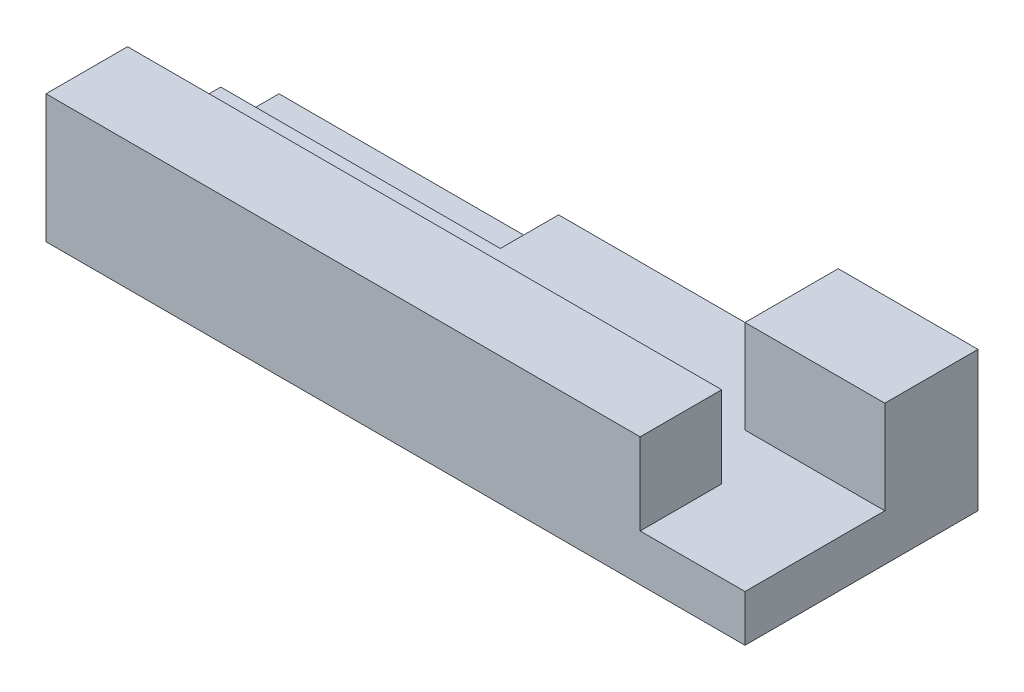
SolidWorks part; units mm, degrees
ref_plane "Front Plane" through (0, 0, 0) normal (0, 0, 1) x (1, 0, 0)
ref_plane "Top Plane" through (0, 0, 0) normal (0, 1, 0) x (1, 0, 0)
ref_plane "Right Plane" through (0, 0, 0) normal (1, 0, 0) x (0, 0, -1)
sketch "Sketch1" plane through (0, 0, 0) normal (0, 1, 0) x (1, 0, 0)
  line L1 (-150, -50) -> (150, -50)
  line L2 (-150, -50) -> (-150, 50)
  line L3 (-150, 50) -> (150, 50)
  line L4 (150, -50) -> (150, 50)
  line L5 (-150, -50) -> (150, 50) construction
  line L6 (-150, 50) -> (150, -50) construction
  line L7 (150, 50) -> (90, 50)
  line L8 (150, 50) -> (150, 10)
  line L9 (150, 10) -> (90, 10)
  line L10 (90, 50) -> (90, 10)
  line L11 (-150, -50) -> (105, -50)
  line L12 (-150, -50) -> (-150, -15)
  line L13 (-150, -15) -> (105, -15)
  line L14 (105, -50) -> (105, -15)
  line L15 (-150, 50) -> (-30, 50)
  line L16 (-150, 50) -> (-150, 25)
  line L17 (-150, 25) -> (-30, 25)
  line L18 (-30, 50) -> (-30, 25)
  point P0 (0, 0)
  dimension "D1" = 100
  dimension "D2" = 300
  dimension "D3" = 40
  dimension "D4" = 60
  dimension "D5" = 25
  dimension "D6" = 120
  dimension "D7" = 255
  dimension "D8" = 35
extrude "Boss-Extrude1" add sketch "Sketch1" along normal blind 20 contours L3 L10 L9 L4 | L3 L18 L17 L2 L13 L14 L1 L4 L9 L10 | L1 L14 L13 L2 | L16 L17 L18 L15 region at (-22.5, 0, 32.5) region at (11.6627, 0, -6.7344) region at (120, 0, -30)
extrude "Boss-Extrude2" add sketch "Sketch1<3>" along normal blind 55 contours L12 L13 L14 L11
sketch "Sketch1<3>" plane through (0, 0, 0) normal (0, 1, 0) x (1, 0, 0) same geometry as "Sketch1"
extrude "Boss-Extrude3" add sketch "Sketch1<5>" along normal blind 60 contours L7 L10 L9 L8
sketch "Sketch1<5>" plane through (0, 0, 0) normal (0, 1, 0) x (1, 0, 0) same geometry as "Sketch1"
extrude "Cut-Extrude1" cut sketch "Sketch1<6>" against normal blind 15 from surface contours L16 L17 L18 L15 starting at face at (48.75, 20, 1.25)
sketch "Sketch1<6>" plane through (0, 0, 0) normal (0, 1, 0) x (1, 0, 0) same geometry as "Sketch1"
